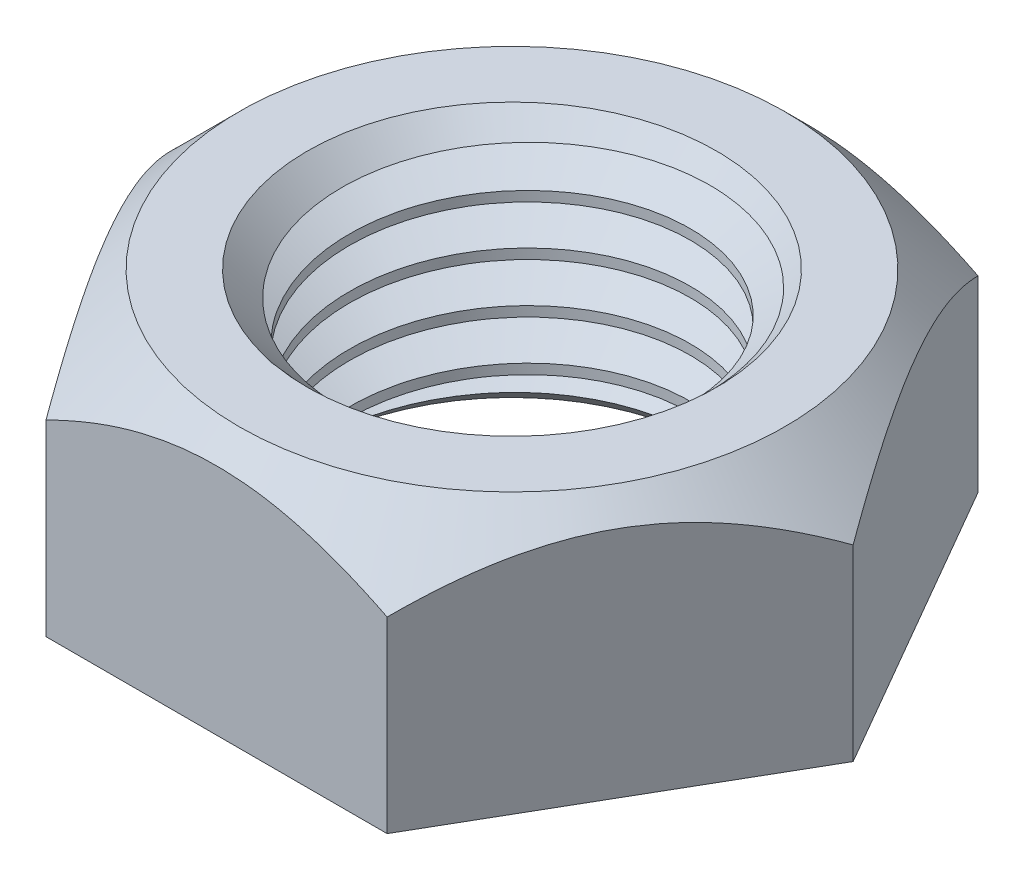
SolidWorks part; units mm, degrees
ref_plane "Front Plane" through (0, 0, 0) normal (0, 0, 1) x (1, 0, 0)
ref_plane "Top Plane" through (0, 0, 0) normal (0, 1, 0) x (1, 0, 0)
ref_plane "Right Plane" through (0, 0, 0) normal (1, 0, 0) x (0, 0, -1)
sketch "Sketch1" plane through (0, 0, 0) normal (0, 1, 0) x (1, 0, 0)
  circle A0 centre (0, 0) radius 6.35
  circle A1 centre (0, 0) radius 12.7
  dimension "D1" = 12.7
  dimension "D2" = 25.4
extrude "Boss-Extrude1" add sketch "Sketch1" along normal blind 9.525
chamfer "Chamfer1" distance 2.54 angle 45 1 edges at (0, 9.525, 12.7)
sketch "Sketch2" plane through (0, 9.525, 0) normal (0, 1, 0) x (1, 0, 0)
  line L1 (-12.7, 0) -> (-6.35, -10.9985)
  line L2 (-6.35, -10.9985) -> (6.35, -10.9985)
  line L3 (6.35, -10.9985) -> (12.7, 0)
  line L4 (12.7, 0) -> (6.35, 10.9985)
  line L5 (6.35, 10.9985) -> (-6.35, 10.9985)
  line L6 (-6.35, 10.9985) -> (-12.7, 0)
  circle A0 centre (0, 0) radius 10.9985 construction
  circle A1 centre (0, 0) radius 12.7 construction
extrude "Cut-Extrude1" cut sketch "Sketch2" against normal through all flip side to cut
chamfer "Chamfer2" distance 1.27 angle 45 2 edges at (0, 0, 6.35) (0, 9.525, 6.35)
ref_plane "Plane2" through (0, 1.27, 0) normal (0, 1, 0) x (1, 0, 0)
sketch "Sketch4" plane through (0, 0, 0) normal (0, 1, 0) x (1, 0, 0)
  circle A0 centre (0, 0) radius 6.35
curve "Helix/Spiral1" pitch 1.8562 height 12.065 radius 6.35 left hand yes centre (0, 0, 0) axis (0, 1, 0) start towards (0, 0, -1)
sketch "Sketch6" plane through (0, 0, 0) normal (1, 0, 0) x (0, 0, -1)
  line L0 (6.096, 0.1466) -> (6.096, -1.6314)
  line L1 (6.096, -1.6314) -> (7.6358, -0.7424)
  line L2 (7.6358, -0.7424) -> (6.096, 0.1466)
  line L3 (7.6358, -0.7424) -> (6.096, -0.7424) construction
  line L4 (6.35, 0) -> (6.35, -1.4847) construction
  dimension "D1" = 60
  dimension "D2" = 0.254
  dimension "D3" = 1.778
sweep "Cut-Sweep1" cut profiles "Sketch6" path "Helix/Spiral1"
